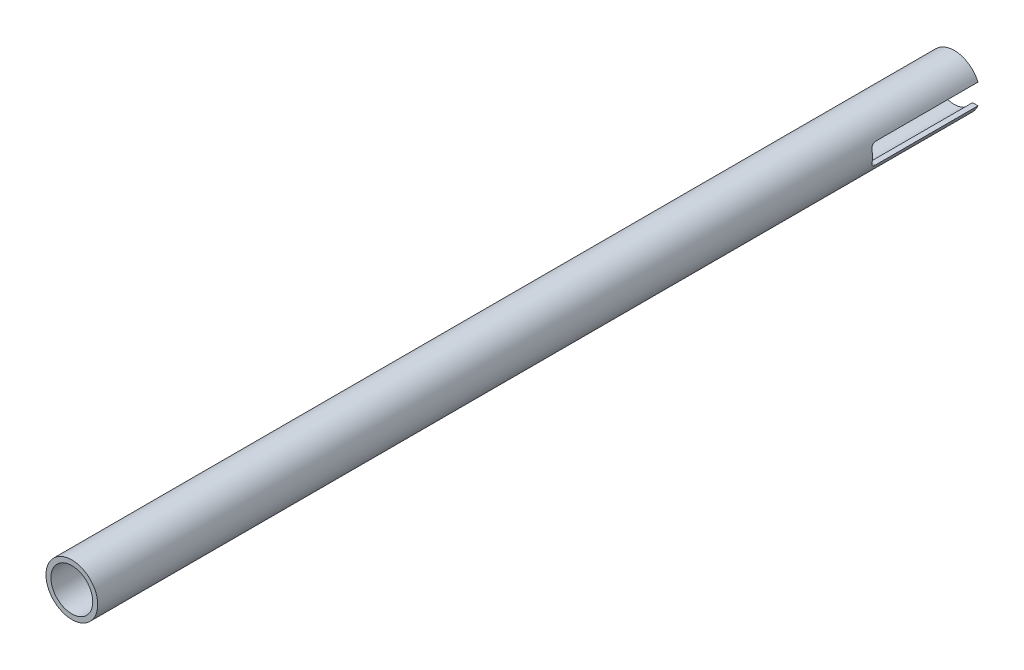
SolidWorks part; units mm, degrees
material "AISI 4130 Steel, annealed at 865C"
ref_plane "Front Plane" through (0, 0, 0) normal (0, 0, 1) x (1, 0, 0)
ref_plane "Top Plane" through (0, 0, 0) normal (0, 1, 0) x (1, 0, 0)
ref_plane "Right Plane" through (0, 0, 0) normal (1, 0, 0) x (0, 0, -1)
sketch "Sketch1" plane through (0, 0, 0) normal (0, 0, 1) x (1, 0, 0)
  circle A0 centre (0, 0) radius 6.477
  circle A1 centre (0, 0) radius 8.001
  dimension "D1" = 12.954
  dimension "D2" = 16.002
extrude "Boss-Extrude1" add sketch "Sketch1" along normal blind 273.05
sketch "Sketch2" plane through (0, 0, 0) normal (1, 0, 0) x (0, 0, -1)
  line L0 (0, 3.175) -> (-31.75, 3.175)
  line L1 (0, 55) -> (0, -55) construction
  line L2 (-31.75, -3.175) -> (0, -3.175)
  line L3 (-33.274, 1.651) -> (-33.274, -1.651)
  line L4 (0, -8.001) -> (0, 8.001) construction
  arc A0 (-33.274, 1.651) -> (-31.75, 3.175) centre (-31.75, 1.651) cw
  arc A1 (-31.75, -3.175) -> (-33.274, -1.651) centre (-31.75, -1.651) cw
  dimension "D5" = 31.75
  dimension "D6" = 33.274
  dimension "D1" = 33.274
  dimension "D2" = 31.75
  dimension "D3" = 6.35
  dimension "D4" = 3.175
extrude "Cut-Extrude1" cut sketch "Sketch2" against normal through all both and the other way through all
